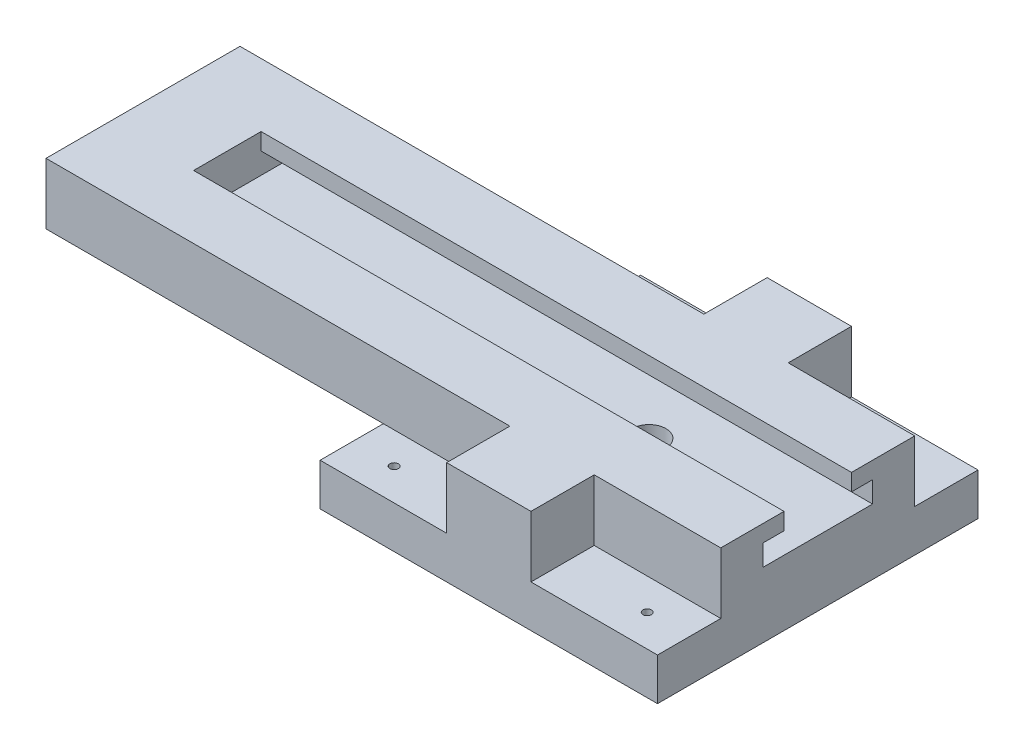
SolidWorks part; units mm, degrees
ref_plane "Front Plane" through (0, 0, 0) normal (0, 0, 1) x (1, 0, 0)
ref_plane "Top Plane" through (0, 0, 0) normal (0, 1, 0) x (1, 0, 0)
ref_plane "Right Plane" through (0, 0, 0) normal (1, 0, 0) x (0, 0, -1)
sketch "Sketch1" plane through (0, 0, 0) normal (0, 1, 0) x (1, 0, 0)
  line L2 (80, -16) -> (220, -16)
  line L3 (220, -16) -> (220, -46)
  line L4 (220, -46) -> (60, -46)
  line L7 (220, 30) -> (220, 0)
  line L8 (80, -16) -> (80, 0)
  line L9 (80, 0) -> (220, 0)
  line L10 (220, 30) -> (60, 30)
  line L11 (60, 30) -> (60, -46)
  point P2 (0, 0)
  point P9 (0, 0)
  dimension "D1" = 16
  dimension "D3" = 30
  dimension "D4" = 160
  dimension "D5" = 140
  dimension "D6" = 160
extrude "Boss-Extrude1" add sketch "Sketch1" along normal blind 4
sketch "Sketch2" plane through (0, 0, 0) normal (0, 1, 0) x (1, 0, 0)
  line L0 (209.7303, -8) -> (-59.5425, -8) construction
  line L1 (220, -8) -> (220, 5) construction
  line L4 (220, 5) -> (220, 30)
  line L5 (220, 30) -> (60, 30)
  line L6 (60, 30) -> (60, -46)
  line L7 (60, 30) -> (60, -46) construction
  line L8 (220, -21) -> (220, -46)
  line L10 (220, -46) -> (60, -46)
  line L11 (220, 5) -> (80, 5)
  line L12 (80, 5) -> (80, -21)
  line L13 (80, -21) -> (220, -21)
  point P18 (0, -8)
  point P19 (60, -8)
  dimension "D1" = 13
extrude "Boss-Extrude2" add sketch "Sketch2" against normal blind 5
sketch "Sketch3" plane through (0, 0, 0) normal (0, 1, 0) x (1, 0, 0)
  line L0 (60, 30) -> (220, 30)
  line L1 (220, 30) -> (220, -46)
  line L2 (220, -46) -> (60, -46)
  line L3 (60, -46) -> (60, 30)
extrude "Boss-Extrude3" add sketch "Sketch3" against normal blind 5.5 from offset 5 offset against normal yes
sketch "Sketch4" plane through (0, 0, 0) normal (0, 1, 0) x (1, 0, 0)
  line L0 (220, 30) -> (220, -46)
  line L1 (220, -46) -> (140, -46)
  line L2 (60, -46) -> (220, -46) construction
  line L3 (140, -46) -> (140, 30)
  line L4 (220, 30) -> (60, 30) construction
  line L5 (140, 30) -> (220, 30)
  dimension "D1" = 80
extrude "Boss-Extrude4" add sketch "Sketch4" against normal blind 10 from offset 10.5 contours L5 L0 L1 L3 offset against normal yes
sketch "Sketch17" plane through (0, 0, 0) normal (0, 1, 0) x (1, 0, 0)
  line L0 (220, -8) -> (180, -8) construction
  line L2 (220, 30) -> (220, -46) construction
  circle A1 centre (180, -8) radius 19
  dimension "D2" = 38
  dimension "D1" = 40
extrude "Boss-Extrude7" add sketch "Sketch17" against normal blind 8 from offset 20.5 offset against normal yes
sketch "Sketch5" plane through (0, 0, 0) normal (0, 1, 0) x (1, 0, 0)
  line L0 (180, -46) -> (180, 30) construction
  line L1 (220, -46) -> (140, -46) construction
  line L2 (140, 30) -> (220, 30) construction
  line L3 (220, -8) -> (140, -8) construction
  line L4 (220, 30) -> (220, -46) construction
  line L5 (140, -46) -> (140, 30) construction
  circle A0 centre (180, -8) radius 10.5
  dimension "D1" = 21
extrude "Cut-Extrude1" cut sketch "Sketch5" against normal blind 12 from offset 25 offset against normal yes
sketch "Sketch7" plane through (0, 0, 0) normal (0, 1, 0) x (1, 0, 0)
  circle A0 centre (180, -8) radius 1.5
  dimension "D1" = 3
extrude "Cut-Extrude2" cut sketch "Sketch7" against normal blind 25 from offset 4 offset against normal yes
sketch "Sketch8" plane through (0, 0, 0) normal (0, 1, 0) x (1, 0, 0)
  circle A0 centre (180, -8) radius 4
  dimension "D1" = 8
extrude "Cut-Extrude3" cut sketch "Sketch8" against normal blind 18.5 from offset 5 offset against normal yes
sketch "Sketch18" plane through (0, 0, 0) normal (0, 1, 0) x (1, 0, 0)
  line L0 (60, 30) -> (170, 30)
  line L1 (60, 30) -> (220, 30) construction
  line L2 (170, 30) -> (170, 15)
  line L3 (170, 15) -> (60, 15)
  line L4 (60, -46) -> (60, 30) construction
  line L5 (60, 15) -> (60, 30)
  line L6 (60, -8) -> (220, -8) construction
  line L8 (170, -46) -> (170, -31)
  line L9 (60, -46) -> (170, -46)
  line L10 (60, -31) -> (60, -46)
  line L11 (170, -31) -> (60, -31)
  line L12 (220, 30) -> (220, 15)
  line L13 (220, 30) -> (220, -46) construction
  line L14 (220, 15) -> (190, 15)
  line L15 (190, 15) -> (190, 30)
  line L16 (190, 30) -> (220, 30)
  line L17 (220, -46) -> (220, -31)
  line L18 (220, -31) -> (190, -31)
  line L19 (190, -46) -> (220, -46)
  line L20 (190, -31) -> (190, -46)
  dimension "D1" = 110
  dimension "D2" = 15
  dimension "D3" = 30
  dimension "D4" = 15
extrude "Cut-Extrude5" cut sketch "Sketch18" against normal blind 14.5 from offset 4
sketch "Sketch9" plane through (0, 0, 0) normal (0, 1, 0) x (1, 0, 0)
  line L0 (180, -8) -> (217.5, -8) construction
  line L1 (217.5, -8) -> (217.5, 29.5) construction
  line L2 (180, -8) -> (142.5, -8) construction
  line L3 (217.5, -8) -> (217.5, -45.5) construction
  line L4 (217.5, 29.5) -> (142.5, 30) construction
  line L5 (60, 30) -> (220, 30) construction
  line L6 (142.5, 30) -> (142.5, -45.5) construction
  line L7 (142.5, -45.5) -> (217.5, -45.5) construction
  line L8 (180, 29.75) -> (180, -45.5) construction
  line L9 (142.5, 22.45) -> (150, 22.45) construction
  line L10 (150, 22.45) -> (150, 29.95) construction
  line L11 (150, -38.45) -> (150, -45.95) construction
  line L12 (142.5, -38.45) -> (150, -38.45) construction
  line L13 (210, 22.45) -> (210, 29.95) construction
  line L14 (217.5, 22.45) -> (210, 22.45) construction
  line L15 (210, -38.45) -> (210, -45.95) construction
  line L16 (217.5, -38.45) -> (210, -38.45) construction
  circle A1 centre (180, -8) radius 30 construction
  circle A2 centre (150, 22.45) radius 1
  circle A3 centre (150, -38.45) radius 1
  circle A4 centre (210, 22.45) radius 1
  circle A5 centre (210, -38.45) radius 1
  dimension "D1" = 37.5
  dimension "D2" = 60
  dimension "D8" = 2
  dimension "D3" = 7.5
  dimension "D4" = 37.5
  dimension "D5" = 37.5
  dimension "D6" = 7.5
  dimension "D7" = 37.5
extrude "Cut-Extrude6" cut sketch "Sketch9" against normal blind 40 from offset 4
